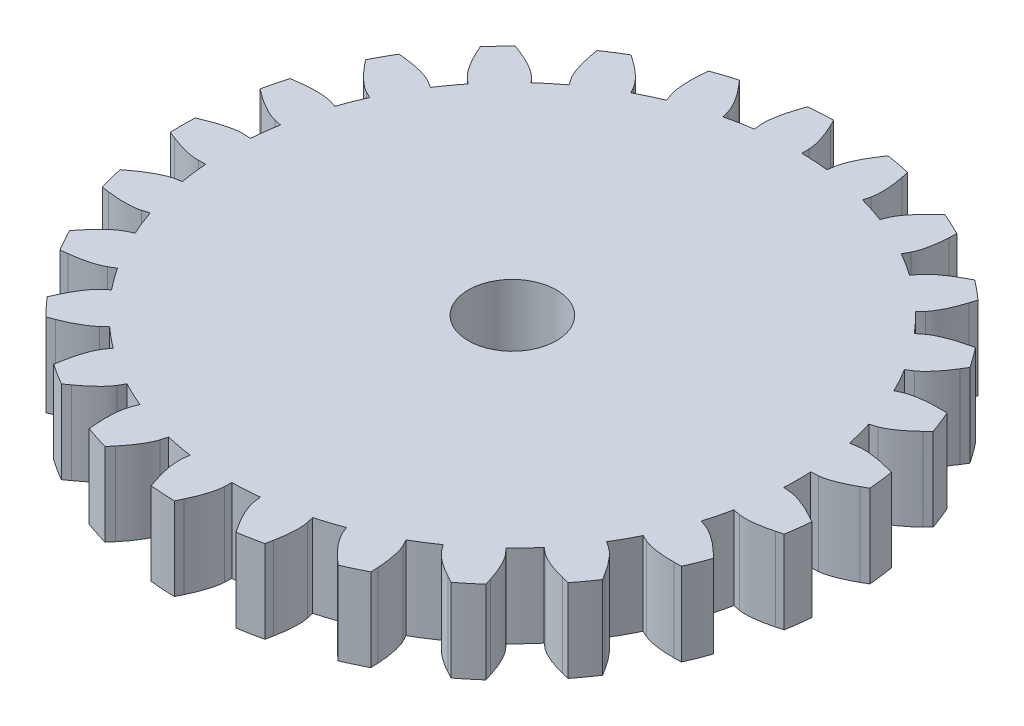
SolidWorks part; units mm, degrees
ref_plane "Front Plane" through (0, 0, 0) normal (0, 0, 1) x (1, 0, 0)
ref_plane "Top Plane" through (0, 0, 0) normal (0, 1, 0) x (1, 0, 0)
ref_plane "Right Plane" through (0, 0, 0) normal (1, 0, 0) x (0, 0, -1)
sketch "Sketch1" plane through (0, 0, 0) normal (0, 1, 0) x (1, 0, 0)
  line L0 (0, 30) -> (-129.8026, 30) construction
  line L1 (-99.777, -6.3159) -> (118.111, 72.9889) construction
  circle A0 centre (0, 0) radius 30
  circle A1 centre (0, 0) radius 28.1908
  dimension "D1" = 60
  dimension "D2" = 20
sketch "Sketch2" plane through (0, 0, 0) normal (0, 1, 0) x (1, 0, 0)
  line L0 (0, 0) -> (-9.6418, 26.4907) construction
  line L1 (-99.777, -6.3159) -> (118.111, 72.9889) construction
  line L2 (-9.6418, 26.4907) -> (0, 30)
  line L3 (-10.3543, 26.2204) -> (0, 0) construction
  line L4 (-10.3543, 26.2204) -> (-0.1021, 30.2689) construction
  line L5 (0, 0) -> (-11.0591, 25.931) construction
  line L6 (0, 0) -> (-11.7559, 25.6226) construction
  line L7 (-12.4441, 25.2955) -> (0, 0) construction
  line L8 (0, 0) -> (-13.1232, 24.95) construction
  line L9 (-8.9223, 26.7416) -> (0.088, 29.7479) construction
  line L10 (-11.0591, 25.931) -> (-0.2192, 30.554) construction
  line L11 (-11.7559, 25.6226) -> (-0.3523, 30.8547) construction
  line L12 (-12.4441, 25.2955) -> (-0.5023, 31.1703) construction
  line L13 (-6.7269, 27.3764) -> (0.2773, 29.0975) construction
  line L14 (-7.4643, 27.1846) -> (0.2256, 29.2961) construction
  line L15 (-5.9846, 27.5482) -> (0.319, 28.9176) construction
  line L16 (-8.1963, 26.973) -> (0.1629, 29.5131) construction
  line L17 (-5.2378, 27.6999) -> (0.3517, 28.7569) construction
  circle A0 centre (0, 0) radius 28.1908 construction
  arc A1 (-9.6418, 26.4907) -> (-10.3543, 26.2204) centre (0, 0) ccw
  arc A2 (-10.3543, 26.2204) -> (-11.0591, 25.931) centre (0, 0) ccw
  arc A3 (-11.0591, 25.931) -> (-11.7559, 25.6226) centre (0, 0) ccw
  arc A4 (-11.7559, 25.6226) -> (-12.4441, 25.2955) centre (0, 0) ccw
  arc A5 (-12.4441, 25.2955) -> (-13.1232, 24.95) centre (0, 0) ccw
  arc A6 (-9.6418, 26.4907) -> (-8.9223, 26.7416) centre (0, 0) cw
  arc A7 (-8.9223, 26.7416) -> (-8.1963, 26.973) centre (0, 0) cw
  arc A8 (-8.1963, 26.973) -> (-7.4643, 27.1846) centre (0, 0) cw
  arc A9 (-7.4643, 27.1846) -> (-6.7269, 27.3764) centre (0, 0) cw
  arc A10 (-6.7269, 27.3764) -> (-5.9846, 27.5482) centre (0, 0) cw
  arc A11 (-5.9846, 27.5482) -> (-5.2378, 27.6999) centre (0, 0) cw
  dimension "D1" = 10.2606
  dimension "D3" = 11.0226
  dimension "D8" = 11.7846
  dimension "D9" = 12.5466
  dimension "D10" = 13.3086
  dimension "D15" = 9.4986
  dimension "D16" = 8.7366
  dimension "D17" = 7.9746
  dimension "D18" = 7.2126
  dimension "D21" = 6.4506
  dimension "D22" = 5.6886
  dimension "D2" = 0.762
  dimension "D4" = 0.762
  dimension "D5" = 0.762
  dimension "D6" = 0.762
  dimension "D7" = 0.762
  dimension "D11" = 0.762
  dimension "D12" = 0.762
  dimension "D13" = 0.762
  dimension "D14" = 0.762
  dimension "D19" = 0.762
  dimension "D20" = 0.762
sketch "Sketch4" plane through (0, 0, 0) normal (0, 1, 0) x (1, 0, 0)
  line L0 (0, 0) -> (0, 39.7853) construction
  line L1 (0, 0) -> (-2.5084, 39.8703) construction
  circle A0 centre (0, 0) radius 28.1908 construction
  circle A1 centre (0, 0) radius 31.81
  circle A2 centre (0, 0) radius 30 construction
  spline S0 degree 3 poles (-0.5023, 31.1703) (-0.4025, 30.9674) (-0.2649, 30.6686) (-0.1033, 30.2758) (-0.0012, 30.0069) (0.0869, 29.7547) (0.1619, 29.52) (0.2247, 29.303) (0.2766, 29.1044) (0.3615, 28.7384) (0.4102, 28.4344) (0.4191, 28.1877) knots 0 0 0 0 0.215965 0.31411 0.405697 0.490726 0.569196 0.641109 0.706463 0.765259 1 1 1 1
  spline S1 degree 3 poles (-3.4083, 30.9875) (-3.4819, 30.7737) (-3.581, 30.46) (-3.692, 30.05) (-3.7597, 29.7704) (-3.8155, 29.5092) (-3.8604, 29.2669) (-3.8956, 29.0438) (-3.9221, 28.8402) (-3.9605, 28.4664) (-3.9707, 28.1588) (-3.9486, 27.9129) knots 0 0 0 0 0.215965 0.31411 0.405697 0.490726 0.569196 0.641109 0.706463 0.765259 1 1 1 1
  spline S2 degree 2 poles (-3.4083, 30.9875) (-3.2603, 31.434) (-3.1869, 31.65) knots 0 0 0 1 1 1
  spline S3 degree 2 poles (-0.5023, 31.1703) (-0.7051, 31.5947) (-0.805, 31.7998) knots 0 0 0 1 1 1
  dimension "D2" = 1.81
  dimension "D1" = 3.6
sketch "Sketch5" plane through (0, 0, 0) normal (0, 1, 0) x (1, 0, 0)
  circle A1 centre (0, 0) radius 27.5
  dimension "D1" = 55
extrude "Boss-Extrude1" add sketch "Sketch5" along normal blind 8
sketch "Sketch7" plane through (0, 0, 0) normal (0, 1, 0) x (1, 0, 0)
  line L0 (0.4191, 28.1877) -> (0.4191, 27.4968)
  circle A2 centre (0, 0) radius 27.5
  arc A3 (0.4191, 27.4968) -> (-3.8796, 27.225) centre (0, 0) ccw
  circle A5 centre (0, 0) radius 31.81
  arc A6 (-0.805, 31.7998) -> (-3.1869, 31.65) centre (0, 0) ccw
  spline S2 degree 2 poles (1274.8199, -2684.1688) (-1275.8104, 2748.1183) (1273.1943, -2684.1016) knots -109.339646 -109.339646 -109.339646 113.20807 113.20807 113.20807 only from (-0.5023, 31.1703) to (-0.805, 31.7998)
  spline S3 degree 2 poles (-0.5023, 31.1703) (-0.7051, 31.5947) (-0.805, 31.7998) knots 0 0 0 1 1 1
  spline S5 degree 3 poles (2998.75, -30.18) (-181.7072, 31.7269) (-13.9419, 63.9356) (-0.1033, 30.2758) (-0.0012, 30.0069) (0.0869, 29.7547) (0.1619, 29.52) (0.2247, 29.303) (0.2766, 29.1044) (3.4004, 15.6431) (-35.1593, -6.9752) (-2993.4136, -158.0668) knots -34.354648 -34.354648 -34.354648 -34.354648 0.215965 0.31411 0.405697 0.490726 0.569196 0.641109 0.706463 0.765259 13.840232 13.840232 13.840232 13.840232 only from (-0.5023, 31.1703) to (0.4191, 28.1877)
  spline S6 degree 3 poles (-0.5023, 31.1703) (-0.4025, 30.9674) (-0.2649, 30.6686) (-0.1033, 30.2758) (-0.0012, 30.0069) (0.0869, 29.7547) (0.1619, 29.52) (0.2247, 29.303) (0.2766, 29.1044) (0.3615, 28.7384) (0.4102, 28.4344) (0.4191, 28.1877) knots 0 0 0 0 0.215965 0.31411 0.405697 0.490726 0.569196 0.641109 0.706463 0.765259 1 1 1 1
  spline S8 degree 2 poles (-928.352, -2822.7807) (921.3197, 2886.35) (-926.7476, -2822.5102) knots -109.339646 -109.339646 -109.339646 113.20807 113.20807 113.20807 only from (-3.4083, 30.9875) to (-3.1869, 31.65)
  spline S9 degree 2 poles (-3.4083, 30.9875) (-3.2603, 31.434) (-3.1869, 31.65) knots 0 0 0 1 1 1
  spline S10 degree 1 poles (-3.9486, 27.9129) (-3.8796, 27.225) knots 0 0 1 1
  spline S11 degree 3 poles (-2971.3214, -405.785) (176.2979, 54.2507) (5.8187, 65.1788) (-3.692, 30.05) (-3.7597, 29.7704) (-3.8155, 29.5092) (-3.8604, 29.2669) (-3.8956, 29.0438) (-3.9221, 28.8402) (-5.3342, 15.0936) (35.7563, -2.5136) (2989.6206, 218.3538) knots -34.354648 -34.354648 -34.354648 -34.354648 0.215965 0.31411 0.405697 0.490726 0.569196 0.641109 0.706463 0.765259 13.840232 13.840232 13.840232 13.840232 only from (-3.4083, 30.9875) to (-3.9486, 27.9129)
  spline S12 degree 3 poles (-3.4083, 30.9875) (-3.4819, 30.7737) (-3.581, 30.46) (-3.692, 30.05) (-3.7597, 29.7704) (-3.8155, 29.5092) (-3.8604, 29.2669) (-3.8956, 29.0438) (-3.9221, 28.8402) (-3.9605, 28.4664) (-3.9707, 28.1588) (-3.9486, 27.9129) knots 0 0 0 0 0.215965 0.31411 0.405697 0.490726 0.569196 0.641109 0.706463 0.765259 1 1 1 1
  dimension "D1" = 0
  dimension "D2" = 0
  dimension "D3" = 0
  dimension "D4" = 0
  dimension "D5" = 0
  dimension "D6" = 0
extrude "Boss-Extrude2" add sketch "Sketch7" along normal up to surface (8 mm away) up to face at (0, 8, 27.5)
sketch "Sketch8" plane through (0, 0, 0) normal (1, 0, 0) x (0, 0, -1)
  line L0 (0, 0) -> (-0.0016, 8) construction
  line L1 (27.4968, 8) -> (-27.5, 8) construction
pattern_circular "CirPattern2" count 25 over 360 about axis through (0, 8, 0) along (0, 1, 0) of "Boss-Extrude2"
sketch "Sketch9" plane through (0, 8, 0) normal (0, 1, 0) x (1, 0, 0)
  circle A0 centre (0, 0) radius 4.25
  dimension "D1" = 8.5
extrude "Cut-Extrude1" cut sketch "Sketch9" against normal through all
equation "\"D3@Sketch2\"=\"D1@Sketch2\"+\"D2@Sketch2\""
equation "\"D4@Sketch2\"=\"D2@Sketch2\""
equation "\"D5@Sketch2\"=\"D2@Sketch2\""
equation "\"D6@Sketch2\"=\"D2@Sketch2\""
equation "\"D7@Sketch2\"=\"D2@Sketch2\""
equation "\"D8@Sketch2\"=\"D3@Sketch2\"+\"D2@Sketch2\""
equation "\"D9@Sketch2\"=\"D8@Sketch2\"+\"D2@Sketch2\""
equation "\"D12@Sketch2\"=\"D11@Sketch2\""
equation "\"D13@Sketch2\"=\"D12@Sketch2\""
equation "\"D14@Sketch2\"=\"D12@Sketch2\""
equation "\"D15@Sketch2\"=\"D1@Sketch2\"-\"D11@Sketch2\""
equation "\"D16@Sketch2\"=\"D15@Sketch2\"-\"D11@Sketch2\""
equation "\"D17@Sketch2\"=\"D16@Sketch2\"-\"D11@Sketch2\""
equation "\"D18@Sketch2\"=\"D17@Sketch2\"-\"D11@Sketch2\""
equation "\"D10@Sketch2\"=\"D1@Sketch2\" + 4*\"D11@Sketch2\""
equation "\"D21@Sketch2\"=\"D18@Sketch2\"-\"D11@Sketch2\""
equation "\"D22@Sketch2\"=\"D21@Sketch2\"-\"D11@Sketch2\""
